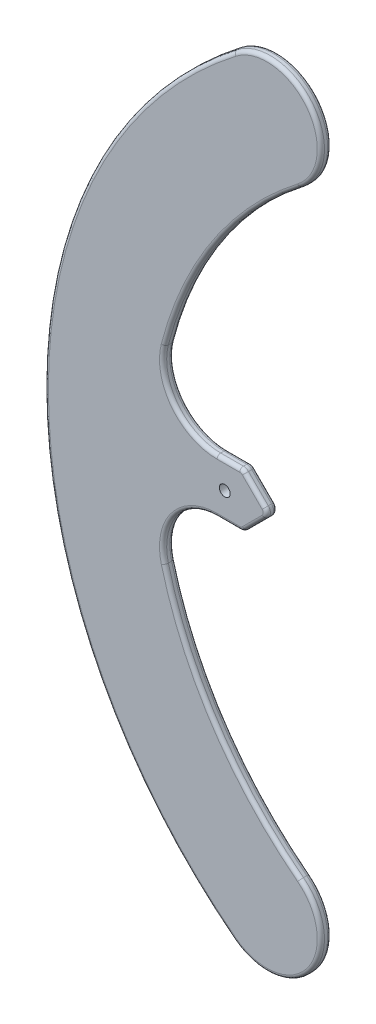
SolidWorks part; units mm, degrees
ref_plane "Front Plane" through (0, 0, 0) normal (0, 0, 1) x (1, 0, 0)
ref_plane "Top Plane" through (0, 0, 0) normal (0, 1, 0) x (1, 0, 0)
ref_plane "Right Plane" through (0, 0, 0) normal (1, 0, 0) x (0, 0, -1)
sketch "Sketch1" plane through (0, 0, 0) normal (0, 0, 1) x (1, 0, 0)
  line L0 (-32.8019, 0) -> (18.2589, 0) construction
  line L1 (70.5, 105) -> (70.5, 135) construction
  line L2 (205.5, -110) -> (-64.5, -110)
  line L3 (205.5, -110) -> (205.5, 110)
  line L4 (205.5, 110) -> (-64.5, 110)
  line L5 (-19.5, 7.5) -> (-19.5, -7)
  line L6 (-19, -7.5) -> (-9.5, -7.5)
  line L7 (-9.5, -7.5) -> (-2, 0)
  line L9 (-9.5, 7.5) -> (-19.5, 7.5)
  line L11 (-19, -7.5) -> (-9.5, -7.5)
  line L15 (-64.5, -110) -> (-64.5, 110)
  line L16 (205.5, -110) -> (-64.5, 110) construction
  line L17 (205.5, 110) -> (-64.5, -110) construction
  line L18 (-18, 7.5) -> (-34.2318, 7.5)
  line L19 (-19, -7.5) -> (-34.2318, -7.5)
  line L60 (-9.5, 7.5) -> (-19.5, 7.5)
  line L162 (-9.5, -7.5) -> (-2, 0)
  line L169 (-2, 0) -> (-9.5, 7.5)
  line L170 (-2, 0) -> (-9.5, 7.5)
  line L176 (-19.5, 7.5) -> (-19.5, -7)
  circle A0 centre (-14.5, 0) radius 1.5 construction
  circle A6 centre (-14.5, 0) radius 1.5
  circle A7 centre (-14.5, 0) radius 1.5
  circle A8 centre (70.5, 0) radius 135
  circle A9 centre (70.5, 0) radius 105
  circle A11 centre (-2.8144, 95) radius 15
  circle A12 centre (-2.8144, -95) radius 15
  arc A22 (-19.5, -7) -> (-19, -7.5) centre (-19, -7) ccw
  arc A25 (-19.5, -7) -> (-19, -7.5) centre (-19, -7) ccw
  point P19 (-64.5, 0)
  point P27 (70.5, 110)
  dimension "D3" = 270
  dimension "D5" = 30
  dimension "D2" = 55
  dimension "D4" = 220
  dimension "D1" = 0
extrude "Boss-Extrude1" add sketch "Sketch1" along normal blind 2.9 contours A11 | A8 A12 A9 A11 | A12 | L18 A9 L19 | L11 L162 L170 A6 region at (-2.8144, -95, 0) region at (-37.1858, 0, 0) region at (-2.8144, 95, 0) region at (-26.9537, -0.0018, 0) region at (-12.3801, 0.002, 0)
fillet "Fillet1" radius 15 2 edges at (-34.2318, -7.5, 1.45) (-34.2318, 7.5, 1.45)
fillet "Fillet2" radius 2 3 edges at (-9.5, -7.5, 1.45) (-9.5, 7.5, 1.45) (-2, 0, 1.45)
fillet "Fillet3" radius 1 28 edges at (-9.5631, 7.3478, 2.9) (-6.1642, 4.1642, 2.9) (-2.8284, 0, 2.9) (-6.1642, -4.1642, 2.9) (-9.5631, -7.3478, 2.9) (-13.4853, -7.5, 2.9) (-28.5007, -13.3144, 2.9) (-17.1494, -57.815, 2.9) (9.0606, -104.1643, 2.9) (-64.5, 0, 2.9) (9.0606, 104.1643, 2.9) (-17.1494, 57.815, 2.9) (-17.1494, 57.815, 0) (9.0606, 104.1643, 0) (-64.5, 0, 0) (9.0606, -104.1643, 0) (-17.1494, -57.815, 0) (-28.5007, -13.3144, 0) (-13.4853, -7.5, 0) (-9.5631, -7.3478, 0) (-6.1642, -4.1642, 0) (-2.8284, 0, 0) (-6.1642, 4.1642, 0) (-9.5631, 7.3478, 0) (-28.5007, 13.3144, 2.9) (-28.5007, 13.3144, 0) (-13.4853, 7.5, 2.9) (-13.4853, 7.5, 0)
